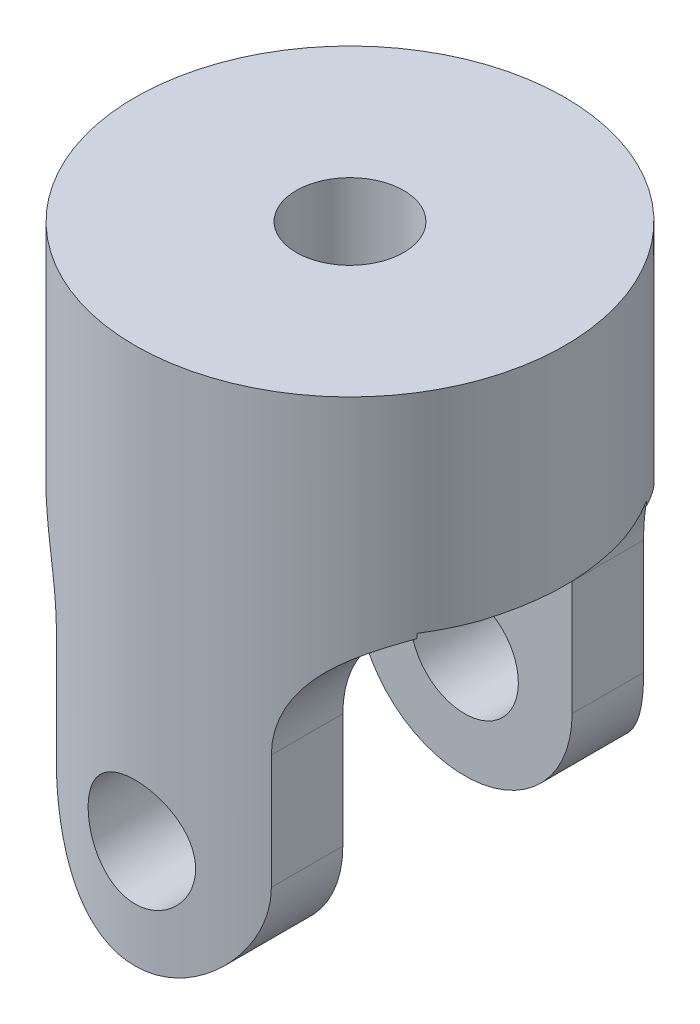
SolidWorks part; units mm, degrees
ref_plane "Front" through (0, 0, 0) normal (0, 0, 1) x (1, 0, 0)
ref_plane "Top" through (0, 0, 0) normal (0, 1, 0) x (-1, 0, 0)
ref_plane "Right" through (0, 0, 0) normal (1, 0, 0) x (0, 0, -1)
other "Configuration Table"
sketch "Sketch1" plane through (0, 0, 0) normal (0, 1, 0) x (-1, 0, 0)
  circle A0 centre (0, 0) radius 19.05
  dimension "D1" = 38.1
extrude "Base-Extrude" add sketch "Sketch1" along normal blind 47.625
sketch "Sketch2" plane through (0, 0, 0) normal (0, 0, 1) x (1, 0, 0)
  line L0 (0, 0) -> (0, 23.7435) construction
  line L1 (9.525, 9.525) -> (9.525, 19.685)
  line L2 (-9.525, 9.525) -> (-9.525, 19.685)
  line L3 (19.05, 29.21) -> (19.05, 0)
  line L4 (-19.05, 47.625) -> (-19.05, 0) construction
  line L5 (-19.05, 0) -> (-19.05, 29.21)
  line L6 (19.05, 0) -> (-19.05, 0) construction
  arc A0 (-9.525, 9.525) -> (9.525, 9.525) centre (0, 9.525) ccw
  arc A1 (9.525, 19.685) -> (19.05, 29.21) centre (19.05, 19.685) cw
  arc A2 (-9.525, 19.685) -> (-19.05, 29.21) centre (-19.05, 19.685) ccw
  dimension "D3" = 9.525
  dimension "D2" = 19.05
  dimension "D4" = 29.21
extrude "Cut-Extrude1" cut sketch "Sketch2" against normal through all and the other way through all flip side to cut
sketch "Sketch8" plane through (0, 0, 0) normal (1, 0, 0) x (0, 0, -1)
  line L0 (-19.05, 0) -> (19.05, 0) construction
  line L1 (-10.16, 0) -> (-10.16, 29.1452)
  line L2 (10.16, 29.1452) -> (-10.16, 29.1452)
  line L3 (10.16, 29.1452) -> (10.16, 0)
  line L4 (0, 0) -> (0, 14.3858) construction
  point P4 (0, 0)
  dimension "D1" = 29.1452
  dimension "D2" = 20.32
extrude "Cut-Extrude5" cut sketch "Sketch8" against normal through all and the other way through all flip side to cut
sketch "Sketch11" plane through (0, 0, 0) normal (0, 0, 1) x (1, 0, 0)
  circle A0 centre (0, 9.525) radius 4.7625
  dimension "D1" = 9.525
extrude "Cut-Extrude6" cut sketch "Sketch11" against normal through all and the other way through all
sketch "Sketch12" plane through (0, 47.625, 0) normal (0, 1, 0) x (-1, 0, 0)
  circle A0 centre (0, 0) radius 4.7625
  dimension "D1" = 9.525
extrude "Cut-Extrude7" cut sketch "Sketch12" against normal through all
ref_axis "Axis1" through (0, 97.625, 0) along (0, -1, 0)
